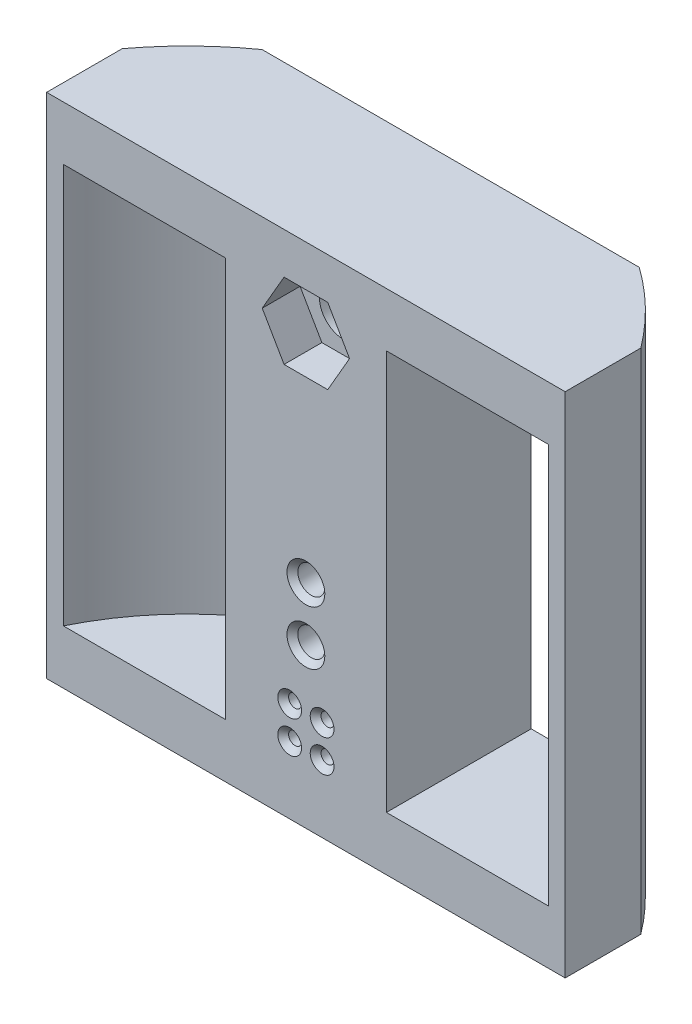
SolidWorks part; units mm, degrees
ref_plane "Front Plane" through (0, 0, 0) normal (0, 0, 1) x (1, 0, 0)
ref_plane "Top Plane" through (0, 0, 0) normal (0, 1, 0) x (1, 0, 0)
ref_plane "Right Plane" through (0, 0, 0) normal (1, 0, 0) x (0, 0, -1)
sketch "Sketch1" plane through (0, 0, 0) normal (0, 0, 1) x (1, 0, 0)
  line L0 (2.175, -128.05) -> (2.175, -128.7)
  line L1 (-2.175, -128.05) -> (-2.175, -128.7)
  line L2 (2.175, -133.05) -> (2.175, -134.025)
  line L3 (-2.175, -133.05) -> (-2.175, -134.025)
  line L11 (-2.175, -128.05) -> (2.175, -128.05)
  line L12 (2.175, -128.05) -> (2.175, -123.7)
  line L13 (2.175, -123.7) -> (-2.175, -123.7)
  line L14 (-2.175, -123.7) -> (-2.175, -128.05)
  line L15 (-2.175, -128.05) -> (2.175, -128.05)
  line L16 (2.175, -128.05) -> (2.175, -123.7)
  line L17 (2.175, -123.7) -> (-2.175, -123.7)
  line L18 (-2.175, -123.7) -> (-2.175, -128.05)
  line L24 (-2.175, -133.05) -> (2.175, -133.05)
  line L25 (2.175, -133.05) -> (2.175, -128.7)
  line L26 (2.175, -128.7) -> (-2.175, -128.7)
  line L27 (-2.175, -128.7) -> (-2.175, -133.05)
  line L28 (-2.175, -133.05) -> (2.175, -133.05)
  line L29 (2.175, -133.05) -> (2.175, -128.7)
  line L30 (2.175, -128.7) -> (-2.175, -128.7)
  line L31 (-2.175, -128.7) -> (-2.175, -133.05)
  line L37 (0, -123.7) -> (0, -142.4) construction
  line L39 (7, -120.55) -> (-7, -120.55)
  line L40 (7, -120.55) -> (7, -145.55)
  line L41 (7, -145.55) -> (-7, -145.55)
  line L42 (-7, -120.55) -> (-7, -145.55)
  line L43 (7, -120.55) -> (-7, -145.55) construction
  line L44 (7, -145.55) -> (-7, -120.55) construction
  line L45 (-1, -142.4) -> (1, -142.4)
  line L46 (1, -142.4) -> (1, -141.625)
  line L47 (1, -141.625) -> (3.8, -141.625)
  line L48 (3.8, -141.625) -> (3.8, -134.025)
  line L49 (3.8, -134.025) -> (-3.8, -134.025)
  line L50 (-3.8, -134.025) -> (-3.8, -141.625)
  line L51 (-3.8, -141.625) -> (-1, -141.625)
  line L52 (-1, -141.625) -> (-1, -142.4)
  line L53 (-1, -142.4) -> (1, -142.4)
  line L54 (1, -142.4) -> (1, -141.625)
  line L55 (1, -141.625) -> (3.8, -141.625)
  line L56 (3.8, -141.625) -> (3.8, -134.025)
  line L57 (3.8, -134.025) -> (-3.8, -134.025)
  line L58 (-3.8, -134.025) -> (-3.8, -141.625)
  line L59 (-3.8, -141.625) -> (-1, -141.625)
  line L60 (-1, -141.625) -> (-1, -142.4)
  circle A0 centre (0, -125.875) radius 1.275
  circle A1 centre (0, -130.875) radius 1.275
  circle A2 centre (-1.5, -139.325) radius 0.65
  circle A3 centre (-1.5, -136.325) radius 0.65
  circle A4 centre (1.5, -136.325) radius 0.65
  circle A5 centre (1.5, -139.325) radius 0.65
  point P25 (0, -133.05)
  dimension "D4" = 2.55
  dimension "D5" = 1.3
  dimension "D6" = 25
  dimension "D7" = 14
  dimension "D1" = 0.1
  dimension "D2" = 0.1
  dimension "D3" = 0.2
extrude "Boss-Extrude1" add sketch "Sketch1" against normal blind 6.4 contours L39 L42 L41 L40 L60 L59 L58 L57 L3 L31 L1 L18 L17 L16 L0 L29 L2 L56 L55 L54 L53 region at (6.7135, -133.05, 0)
sketch "Sketch3" plane through (0, 0, 0) normal (0, 0, 1) x (1, 0, 0)
  line L4 (7, -120.55) -> (-7, -120.55)
  line L5 (-7, -120.55) -> (-7, -145.55)
  line L6 (-7, -145.55) -> (7, -145.55)
  line L7 (7, -145.55) -> (7, -120.55)
  line L8 (7, -120.55) -> (-7, -120.55)
  line L9 (-7, -120.55) -> (-7, -145.55)
  line L10 (-7, -145.55) -> (7, -145.55)
  line L11 (7, -145.55) -> (7, -120.55)
  circle A0 centre (-1.5, -139.325) radius 0.6
  circle A1 centre (-1.5, -136.325) radius 0.6
  circle A2 centre (1.5, -136.325) radius 0.6
  circle A3 centre (1.5, -139.325) radius 0.6
  circle A4 centre (0, -130.875) radius 1.25
  circle A5 centre (0, -125.875) radius 1.25
  dimension "D2" = 2.5
  dimension "D3" = 1.2
  dimension "D1" = 0
extrude "Boss-Extrude3" add sketch "Sketch3" along normal blind 7
chamfer "Chamfer1" distance 0.5 angle 45 6 edges at (2.1, -139.325, 7) (-0.9, -139.325, 7) (-0.9, -136.325, 7) (2.1, -136.325, 7) (1.25, -130.875, 7) (1.25, -125.875, 7)
sketch "Sketch4" plane through (0, -145.55, 0) normal (0, -1, 0) x (1, 0, 0)
  line L0 (-7, -6.4) -> (-17.4539, -6.4)
  line L1 (-7, 7) -> (-27.9106, 7)
  line L2 (7, -6.4) -> (17.4539, -6.4)
  line L3 (7, 7) -> (27.9106, 7)
  line L4 (-24, 0) -> (-24, 7)
  line L5 (24, 0) -> (24, 7)
  circle A4 centre (0, 18) radius 30
  arc A5 (-24, 0) -> (24, 0) centre (0, 18) ccw construction
  line M2 (7, -6.4) -> (7, 7)
  line M4 (-7, 7) -> (-7, -6.4)
extrude "Boss-Extrude4" add sketch "Sketch4" against normal up to surface (25 mm away) contours L1 A4 L0 M4 | L2 A4 L3 M2 region at (-14.9215, -145.55, 0.7207) region at (14.9215, -145.55, 0.7207) up to face at (0, -120.55, 0.3)
sketch "Sketch5" plane through (0, -120.55, 0) normal (0, 1, 0) x (1, 0, 0)
  line L2 (17.4539, 6.4) -> (-17.4539, 6.4)
  line L3 (-24, -7) -> (24, -7)
  line L4 (17.4539, 6.4) -> (-17.4539, 6.4)
  line L5 (-24, -7) -> (24, -7)
  line L8 (-24, 0) -> (-24, -7)
  line L9 (-24, 0) -> (-24, -7)
  line L10 (24, -7) -> (24, 0)
  line L11 (24, -7) -> (24, 0)
  arc A2 (-17.4539, 6.4) -> (-24, 0) centre (0, -18) ccw
  arc A3 (24, 0) -> (17.4539, 6.4) centre (0, -18) ccw
  arc A4 (-17.4539, 6.4) -> (-24, 0) centre (0, -18) ccw
  arc A5 (24, 0) -> (17.4539, 6.4) centre (0, -18) ccw
  dimension "D1" = 0
extrude "Boss-Extrude5" add sketch "Sketch5" along normal blind 22
sketch "Sketch6" plane through (0, 0, 7) normal (0, 0, 1) x (1, 0, 0)
  line L0 (0, -98.55) -> (0, -145.55) construction
  line L1 (-24, -98.55) -> (24, -98.55) construction
  line L2 (-24, -145.55) -> (24, -145.55) construction
  circle A0 centre (0, -105.875) radius 2.25
  circle A2 centre (0, -105.875) radius 2.25 construction
  dimension "D2" = 4.5
extrude "Cut-Extrude1" cut sketch "Sketch6" against normal up to next
sketch "Sketch7" plane through (0, 0, 7) normal (0, 0, 1) x (1, 0, 0)
  line L1 (4.0415, -105.875) -> (2.0207, -102.375)
  line L2 (2.0207, -102.375) -> (-2.0207, -102.375)
  line L3 (-2.0207, -102.375) -> (-4.0415, -105.875)
  line L4 (-4.0415, -105.875) -> (-2.0207, -109.375)
  line L5 (-2.0207, -109.375) -> (2.0207, -109.375)
  line L6 (2.0207, -109.375) -> (4.0415, -105.875)
  circle A0 centre (0, -105.875) radius 3.5 construction
  dimension "D1" = 7
extrude "Cut-Extrude2" cut sketch "Sketch7" against normal blind 3.5
ref_plane "Plane1" through (0, -103.55, 0) normal (0, 1, 0) x (1, 0, 0)
sketch "Sketch8" plane through (0, -103.55, 0) normal (0, 1, 0) x (1, 0, 0)
  line L2 (-12.4539, 6.4) -> (-12.4539, 3.6772)
  line L3 (17.4539, 6.4) -> (-17.4539, 6.4) construction
  line L4 (15.7683, 1.4) -> (-15.7683, 1.4)
  line L5 (-19, -2) -> (19, -2)
  line L6 (15.7683, 1.4) -> (-15.7683, 1.4)
  line L7 (-19, -2) -> (19, -2)
  line L8 (0, 6.4) -> (0, -7) construction
  line L9 (-24, -7) -> (24, -7) construction
  line L10 (12.4539, 6.4) -> (12.4539, 3.6772)
  line L11 (-7.4539, 6.4) -> (-7.4539, -7)
  line L12 (7.4539, 6.4) -> (7.4539, -7)
  line L13 (-12.4539, 6.4) -> (12.4539, 6.4)
  line L14 (-22.4499, -7) -> (22.4499, -7)
  line L19 (-19, -1.7519) -> (-19, -2)
  line L20 (-19, -1.7519) -> (-19, -2)
  line L21 (19, -2) -> (19, -1.7519)
  line L22 (19, -2) -> (19, -1.7519)
  circle A2 centre (0, -18) radius 25
  arc A4 (19, -1.7519) -> (15.7683, 1.4) centre (0, -18) ccw
  arc A5 (-15.7683, 1.4) -> (-19, -1.7519) centre (0, -18) ccw
  arc A6 (19, -1.7519) -> (15.7683, 1.4) centre (0, -18) ccw
  arc A7 (-15.7683, 1.4) -> (-19, -1.7519) centre (0, -18) ccw
  dimension "D2" = 5
  dimension "D3" = 5
  dimension "D1" = 5
extrude "Cut-Extrude3" cut sketch "Sketch8" against normal offset from surface (37 mm away) 5 contours A2 L11 L13 L2 | L11 A2 L6 | L6 A2 L7 L11 | L7 A2 L14 L11 | A2 L10 L13 L12 | A2 L12 L6 | L7 A2 L6 L12 | L14 A2 L7 L12 region at (-10.5509, -103.55, -5.5085) region at (-10.4201, -103.55, -3.0071) region at (-12.5705, -103.55, 0.3946) region at (-14.2467, -103.55, 4.5984) region at (10.4201, -103.55, -3.0071) region at (12.5705, -103.55, 0.3946) region at (10.5509, -103.55, -5.5085) region at (14.2467, -103.55, 4.5984) up to face at (0, -145.55, 0.1163)
